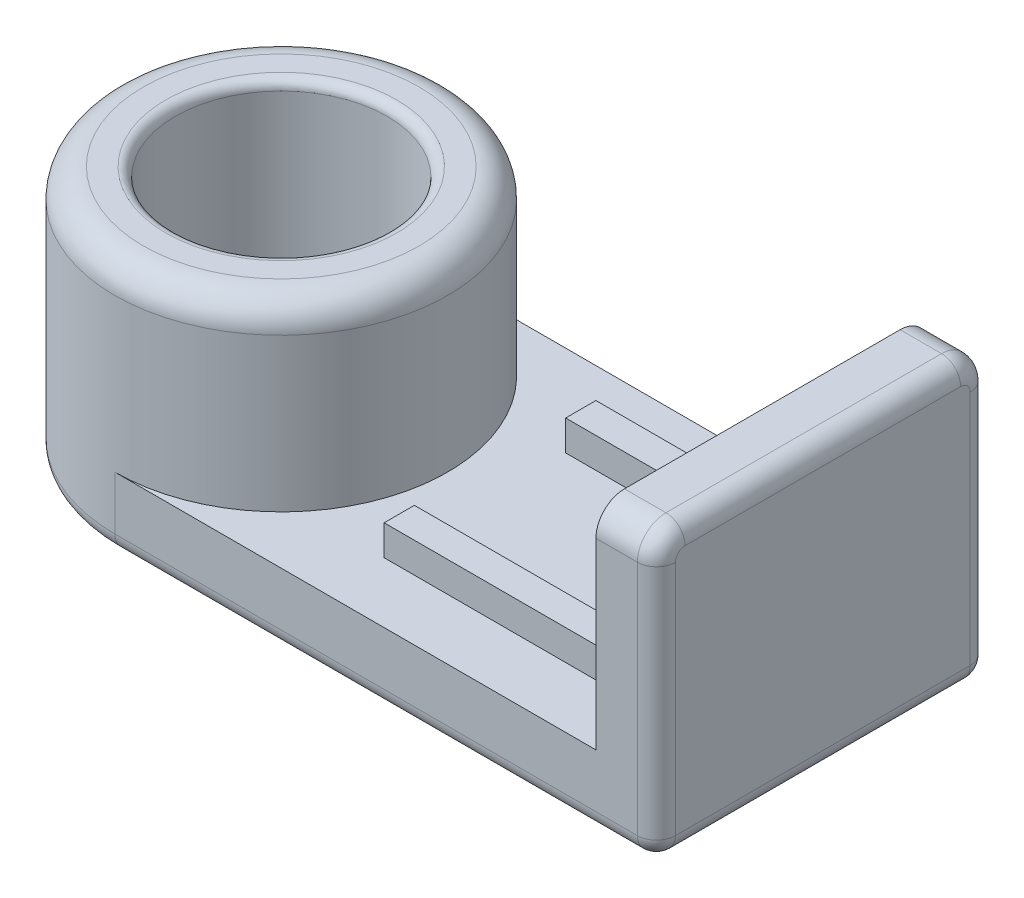
SolidWorks part; units mm, degrees
ref_plane "Front Plane" through (0, 0, 0) normal (0, 0, 1) x (1, 0, 0)
ref_plane "Top Plane" through (0, 0, 0) normal (0, 1, 0) x (1, 0, 0)
ref_plane "Right Plane" through (0, 0, 0) normal (1, 0, 0) x (0, 0, -1)
sketch "Sketch1" plane through (0, 0, 0) normal (0, 1, 0) x (1, 0, 0)
  line L0 (-19.685, 17.4625) -> (-19.685, -17.4625) construction
  line L2 (37.1475, -17.4625) -> (37.1475, 17.4625)
  line L4 (-19.685, 17.4625) -> (37.1475, 17.4625)
  line L7 (-19.685, -17.4625) -> (37.1475, -17.4625)
  arc A0 (-19.685, 17.4625) -> (-19.685, -17.4625) centre (-19.685, 0) ccw
  point P0 (0, 0)
extrude "Boss-Extrude1" add sketch "Sketch1" along normal blind 7.62
sketch "Sketch4" plane through (0, 7.62, 0) normal (0, 1, 0) x (1, 0, 0)
  line L0 (-19.685, -17.4625) -> (37.1475, -17.4625) construction
  line L1 (37.1475, 17.4625) -> (30.7975, 17.4625)
  line L2 (37.1475, 17.4625) -> (37.1475, -17.4625)
  line L3 (37.1475, -17.4625) -> (30.7975, -17.4625)
  line L4 (30.7975, 17.4625) -> (30.7975, -17.4625)
  dimension "D1" = 6.35
extrude "Boss-Extrude3" add sketch "Sketch4" along normal blind 12.7
sketch "Sketch5" plane through (0, 7.62, 0) normal (0, 1, 0) x (1, 0, 0)
  line L0 (-19.685, 17.4625) -> (-19.685, -17.4625) construction
  circle A0 centre (-19.685, 0) radius 11.1125
extrude "Cut-Extrude1" cut sketch "Sketch5" against normal blind 12.7
sketch "Sketch6" plane through (0, 7.62, 0) normal (0, 1, 0) x (1, 0, 0)
  line L1 (27.6225, 11.1125) -> (2.2225, 11.1125)
  line L2 (27.6225, 11.1125) -> (27.6225, 7.9375)
  line L3 (27.6225, 7.9375) -> (2.2225, 7.9375)
  line L4 (2.2225, 11.1125) -> (2.2225, 7.9375)
  dimension "D1" = 25.4
  dimension "D2" = 3.175
  dimension "D3" = 3.175
  dimension "D4" = 6.35
extrude "Boss-Extrude4" add sketch "Sketch6" along normal blind 3.175
sketch "Sketch7" plane through (0, 7.62, 0) normal (0, 1, 0) x (1, 0, 0)
  line L1 (27.6225, -11.1125) -> (2.2225, -11.1125)
  line L2 (27.6225, -11.1125) -> (27.6225, -7.9375)
  line L3 (27.6225, -7.9375) -> (2.2225, -7.9375)
  line L4 (2.2225, -11.1125) -> (2.2225, -7.9375)
  dimension "D1" = 3.175
  dimension "D2" = 25.4
  dimension "D3" = 3.175
  dimension "D4" = 6.35
extrude "Boss-Extrude5" add sketch "Sketch7" along normal blind 3.175
sketch "Sketch10" plane through (0, 20.32, 0) normal (0, 1, 0) x (1, 0, 0)
  line L1 (30.7975, 17.4625) -> (37.1475, 17.4625)
  line L2 (30.7975, 17.4625) -> (30.7975, -17.4625)
  line L3 (30.7975, -17.4625) -> (37.1475, -17.4625)
  line L4 (37.1475, 17.4625) -> (37.1475, -17.4625)
extrude "Boss-Extrude8" add sketch "Sketch10" along normal blind 9.525
fillet "Fillet1" radius 2 3 edges at (37.1475, 14.9225, 17.4625) (37.1475, 14.9225, -17.4625) (37.1475, 29.845, 0)
fillet "Fillet2" radius 2 6 edges at (36.5617, 0, -16.8767) (37.1475, 0, 0) (36.5617, 0, 16.8767) (7.7312, 0, 17.4625) (-37.1475, 0, 0) (7.7312, 0, -17.4625)
sketch "Sketch11" plane through (0, 7.62, 0) normal (0, 1, 0) x (1, 0, 0)
  circle A0 centre (-19.685, 0) radius 17.4625
extrude "Boss-Extrude9" add sketch "Sketch11" along normal blind 19.05
sketch "Sketch12" plane through (0, 7.62, 0) normal (0, -1, 0) x (-1, 0, 0)
  line L0 (30.7975, 0) -> (8.5725, 0) construction
  circle A0 centre (19.685, 0) radius 11.1125 construction
  circle A1 centre (19.685, 0) radius 11.1125
  dimension "D1" = 22.225
extrude "Cut-Extrude2" cut sketch "Sketch12" against normal through all
fillet "Fillet3" radius 1 2 edges at (-19.685, 26.67, 11.1125) (-19.685, 0, 11.1125)
fillet "Fillet4" radius 3 1 edges at (-19.685, 26.67, 17.4625)
fillet "Fillet5" radius 3 4 edges at (36.5617, 29.2592, 16.8767) (36.5617, 29.2592, -16.8767) (32.9725, 29.845, -17.4625) (32.9725, 29.845, 17.4625)
